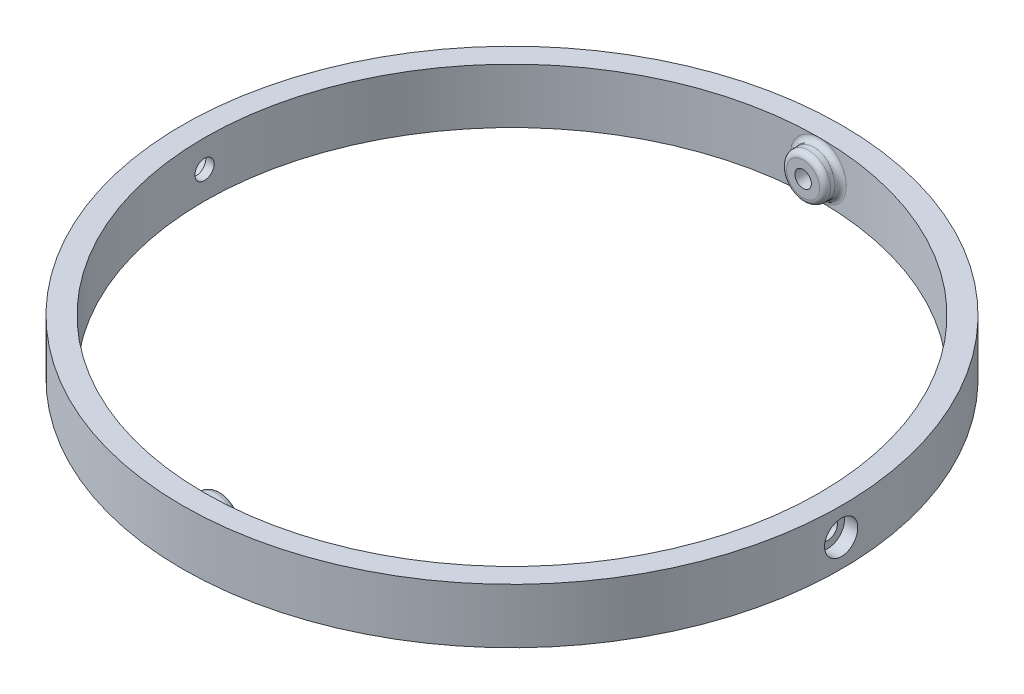
SolidWorks part; units mm, degrees
ref_plane "Front Plane" through (0, 0, 0) normal (0, 0, 1) x (1, 0, 0)
ref_plane "Top Plane" through (0, 0, 0) normal (0, 1, 0) x (1, 0, 0)
ref_plane "Right Plane" through (0, 0, 0) normal (1, 0, 0) x (0, 0, -1)
sketch "Sketch1" plane through (0, 0, 0) normal (0, 1, 0) x (1, 0, 0)
  line L0 (0, 0) -> (11.2101, 0) construction
  line L1 (0, 0) -> (0, 12.8983) construction
  circle A0 centre (0, 0) radius 60
  circle A1 centre (0, 0) radius 56
  dimension "D1" = 120
  dimension "D2" = 4
extrude "Boss-Extrude1" add sketch "Sketch1" along normal blind 10 contours A0 | A1
sketch "Sketch2" plane through (0, 0, 0) normal (0, 0, 1) x (1, 0, 0)
  line L0 (0, 0) -> (0, 16.6364) construction
  circle A0 centre (0, 5) radius 1.5
  dimension "D1" = 3
  dimension "D2" = 5
sketch "Sketch3" plane through (0, 0, 0) normal (1, 0, 0) x (0, 0, -1)
  line L0 (0, 0) -> (0, 15.571) construction
  circle A0 centre (0, 5) radius 1.75
  dimension "D1" = 3.5
  dimension "D2" = 5
extrude "Cut-Extrude2" cut sketch "Sketch3" against normal through all both and the other way through all
ref_plane "Plane1" through (-60, 0, 0) normal (1, 0, 0) x (0, 0, -1)
sketch "Sketch4" plane through (-60, 0, 0) normal (1, 0, 0) x (0, 0, -1)
  line L0 (0, 0) -> (0, 10) construction
  line L1 (60, 10) -> (-60, 10) construction
  circle A0 centre (0, 5) radius 3.025
  dimension "D1" = 6.05
extrude "Cut-Extrude3" cut sketch "Sketch4" along normal blind 2.5
mirror "Mirror1" about plane through (0, 0, 0) normal (1, 0, 0) of "Cut-Extrude3"
extrude "Cut-Extrude4" cut sketch "Sketch2" against normal blind 58
extrude "Cut-Extrude5" cut sketch "Sketch2<2>" along normal blind 58
sketch "Sketch2<2>" plane through (0, 0, 0) normal (0, 0, 1) x (1, 0, 0) same geometry as "Sketch2"
ref_plane "Plane2" through (0, 0, 56) normal (0, 0, 1) x (1, 0, 0)
sketch "Sketch5" plane through (0, 0, 56) normal (0, 0, 1) x (1, 0, 0)
  line L0 (0, 0) -> (0, 10) construction
  line L1 (60, 10) -> (-60, 10) construction
  circle A0 centre (0, 5) radius 4
  circle A1 centre (0, 5) radius 5 construction
  circle A2 centre (0, 5) radius 1.5
  dimension "D1" = 8
  dimension "D2" = 3
extrude "Boss-Extrude2" add sketch "Sketch5" against normal blind 3
fillet "Fillet1" radius 1 1 edges at (4, 5, 53)
fillet "Fillet2" radius 1 1 edges at (-3.8954, 5.9086, 55.8643)
mirror "Mirror2" about plane through (0, 0, 0) normal (0, 0, 1) of "Fillet2", "Fillet1", "Boss-Extrude2"
